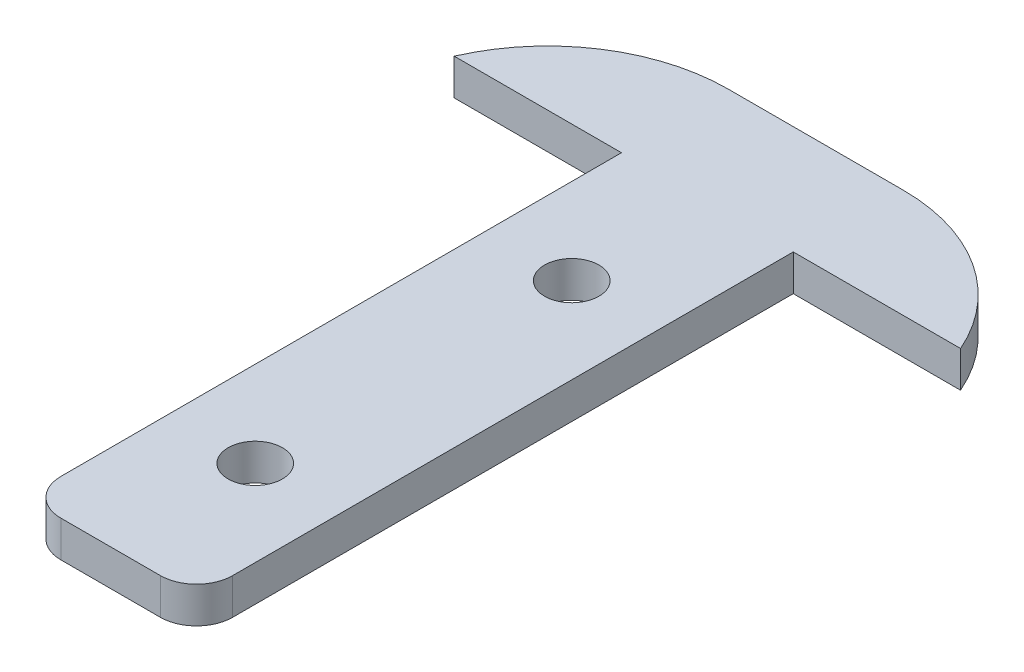
SolidWorks part; units mm, degrees
ref_plane "Front Plane" through (0, 0, 0) normal (0, 0, 1) x (1, 0, 0)
ref_plane "Top Plane" through (0, 0, 0) normal (0, 1, 0) x (1, 0, 0)
ref_plane "Right Plane" through (0, 0, 0) normal (1, 0, 0) x (0, 0, -1)
sketch "Sketch1" plane through (0, 0, 0) normal (0, 1, 0) x (1, 0, 0)
  line L1 (4.75, -16.5) -> (-4.75, -16.5)
  line L2 (4.75, -16.5) -> (4.75, 16.5)
  line L3 (4.75, 16.5) -> (-4.75, 16.5)
  line L4 (-4.75, -16.5) -> (-4.75, 16.5)
  line L5 (4.75, -16.5) -> (-4.75, 16.5) construction
  line L6 (4.75, 16.5) -> (-4.75, -16.5) construction
  line L8 (-14, 16.5) -> (14, 16.5)
  line L9 (-14, 16.5) -> (-14, 22.5)
  line L10 (-14, 22.5) -> (14, 22.5)
  line L11 (14, 16.5) -> (14, 22.5)
  point P0 (0, 0)
  point P9 (0, 16.5)
  point P10 (0, 16.5)
  dimension "D1" = 6
  dimension "D2" = 9.5
  dimension "D3" = 33
  dimension "D4" = 28
extrude "Boss-Extrude2" add sketch "Sketch1" along normal blind 2 contours L3 | L4 L1 L2 L3 region at (0, 0, 0) region at (0, 0, -19.5)
sketch "Sketch2" plane through (0, 0, 0) normal (0, -1, 0) x (1, 0, 0)
  line L0 (-4.75, -16.5) -> (4.75, -16.5) construction
  line L2 (4.75, 16.5) -> (4.75, -16.5) construction
  line L3 (4.75, -16.5) -> (14, -16.5) construction
  line L4 (4.75, -16.5) -> (0, -16.5) construction
  line L5 (0, -16.5) -> (0, -9) construction
  line L6 (0, 16.5) -> (0, 8.5) construction
  line L7 (4.75, 16.5) -> (-4.75, 16.5) construction
  circle A1 centre (0, 8.5) radius 1.5
  circle A2 centre (0, -9) radius 1.5
extrude "Cut-Extrude1" cut sketch "Sketch2" against normal through all
fillet "Fillet6" radius 10 1 edges at (14, 1, -22.5)
fillet "Fillet7" radius 10 1 edges at (-14, 1, -22.5)
fillet "Fillet10" radius 2 2 edges at (4.75, 1, 16.5) (-4.75, 1, 16.5)
